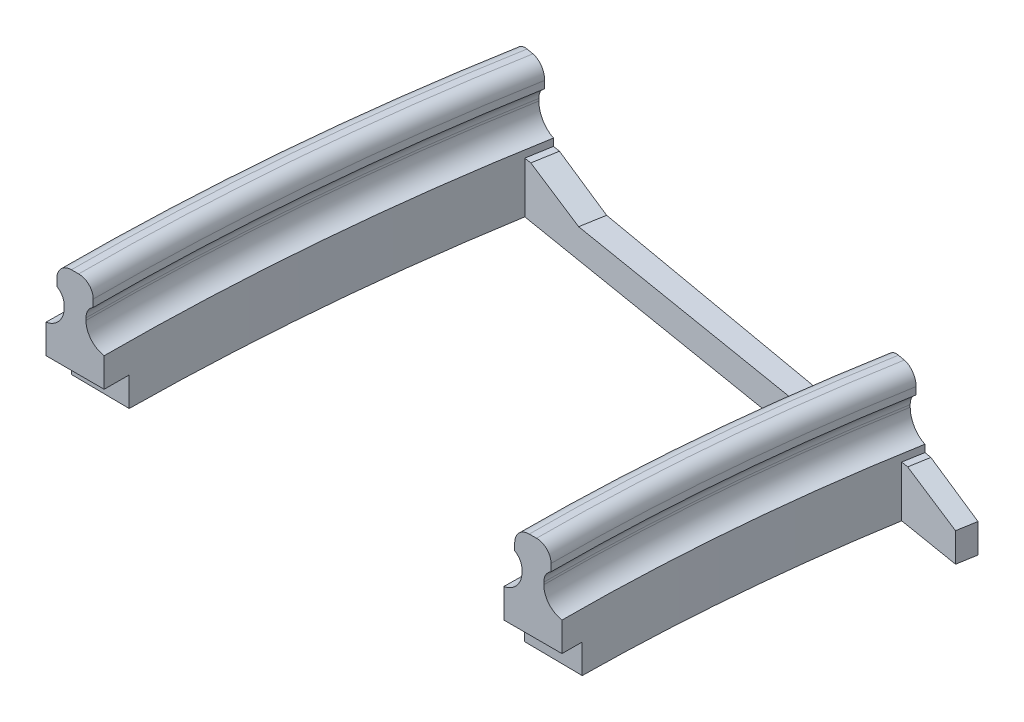
SolidWorks part; units mm, degrees
other "标注1"
sketch "草图3" plane through (-22.25, 4, -10) normal (-0.231, 0.6469, -0.7268) x (-0.9696, -0.2151, 0.1167)
ref_plane "前视基准面" through (0, 0, 0) normal (0, 0, 1) x (1, 0, 0)
ref_plane "上视基准面" through (0, 0, 0) normal (0, 1, 0) x (1, 0, 0)
ref_plane "右视基准面" through (0, 0, 0) normal (1, 0, 0) x (0, 0, -1)
other "Configuration Table"
sketch "草图4" plane through (0, 0, 0) normal (0, 0, 1) x (1, 0, 0)
  line L0 (0, 0) -> (31.5, 0) construction
  line L1 (0.75, -1.5) -> (1.25, -1.5)
  line L3 (0, 0) -> (1.25, 0)
  line L4 (1.25, -1.5) -> (1.25, 0)
  line L5 (0, 0) -> (-1.25, 0)
  line L10 (0.75, -1.5) -> (0.75, -4)
  line L11 (-0.75, -1.5) -> (-1.25, -1.5)
  line L12 (0.75, -4) -> (2, -4)
  line L14 (0, -8) -> (2, -8)
  line L15 (2, -4) -> (2, -8)
  line L16 (-1.25, 0) -> (-1.25, -1.5)
  line L20 (-0.75, -1.5) -> (-0.75, -4)
  line L21 (-0.75, -4) -> (-2, -4)
  line L23 (0, -8) -> (-2, -8)
  line L24 (-2, -4) -> (-2, -8)
  line L25 (31.5, 0) -> (32.75, 0)
  line L26 (30.25, 0) -> (31.5, 0)
  line L27 (30.25, 0) -> (30.25, -1.5)
  line L28 (30.25, -1.5) -> (30.75, -1.5)
  line L31 (30.75, -1.5) -> (30.75, -4)
  line L34 (29.5, -4) -> (30.75, -4)
  line L35 (29.5, -4) -> (29.5, -8)
  line L36 (29.5, -8) -> (31.5, -8)
  line L39 (32.25, -1.5) -> (32.75, -1.5)
  line L40 (32.75, 0) -> (32.75, -1.5)
  line L42 (32.25, -1.5) -> (32.25, -4)
  line L45 (32.25, -4) -> (33.5, -4)
  line L47 (31.5, -8) -> (33.5, -8)
  line L48 (33.5, -4) -> (33.5, -8)
  point P0 (0, 0)
  point P2 (15.75, 0)
  dimension "D1" = 1.25
  dimension "D4" = 2.5
sketch "草图6" plane through (0, 0, 0) normal (0, 0, 1) x (1, 0, 0)
  line L0 (165.75, 3.8535) -> (165.75, -12.2756)
  dimension "D1" = 150
revolve "旋转1" add sketch "草图4" angle 10 about L0
fillet "圆角1" radius 1.5 2 edges at (1.3779, -4, -14.3807) (-0.1164, -4, -14.5114)
fillet "圆角2" radius 1.5 2 edges at (31.2637, -4, -11.766) (32.758, -4, -11.6353)
fillet "圆角3" radius 1 4 edges at (33.2561, 0, -11.5917) (30.7656, 0, -11.8096) (31.2637, -1.5, -11.766) (32.758, -1.5, -11.6353)
fillet "圆角4" radius 1 4 edges at (1.876, 0, -14.3371) (-0.1164, -1.5, -14.5114) (1.3779, -1.5, -14.3807) (-0.6145, 0, -14.555)
sketch "草图7" plane through (0, 0, 0) normal (0, 0, 1) x (1, 0, 0)
  line L1 (-2, -8) -> (2, -8)
  line L2 (-2, -8) -> (-2, -6)
  line L3 (-2, -6) -> (2, -6)
  line L4 (2, -8) -> (2, -6)
  line L5 (33.5, -8) -> (33.5, -4) construction
  line L6 (29.5, -8) -> (33.5, -8)
  line L7 (29.5, -8) -> (29.5, -6)
  line L8 (29.5, -6) -> (33.5, -6)
  line L9 (33.5, -8) -> (33.5, -6)
  line L10 (2, -8) -> (2, -4) construction
  dimension "D1" = 2
sketch "草图9" plane through (0, 0, 0) normal (0, 1, 0) x (1, 0, 0)
  line L0 (29.5, 0) -> (2, 0)
  line L1 (-2, 0) -> (2, 0) construction
  line L2 (4.4877, 28.4349) -> (31.5699, 23.6596)
  line L3 (18.0288, 26.0472) -> (15.75, 0)
  arc A0 (4.4877, 28.4349) -> (2, 0) centre (165.75, 0) ccw construction
  arc A1 (31.5699, 23.6596) -> (29.5, 0) centre (165.75, 0) ccw construction
  point P20 (165.75, 0)
  dimension "D1" = 10
  dimension "D2" = 26.1467
revolve "切除-旋转1" cut sketch "草图7" angle 0.6 about L0
sketch "草图10" plane through (0, -6, 0) normal (0, -1, 0) x (1, 0, 0)
  line L0 (-1.9977, -0.8783) -> (2.0022, -0.8574) construction
  line L2 (2.0022, -0.8574) -> (29.5019, -0.7134) construction
  line L3 (29.5019, -0.7134) -> (33.5018, -0.6925) construction
  circle A1 centre (0.0023, -0.8679) radius 0.4
  circle A2 centre (31.5018, -0.7029) radius 0.4
  arc A3 (-2, 0) -> (-1.9908, -1.7566) centre (165.75, 0) ccw construction
  arc A4 (2, 0) -> (2.009, -1.7148) centre (165.75, 0) ccw construction
  arc A5 (29.5, 0) -> (29.5075, -1.4268) centre (165.75, 0) ccw construction
  arc A6 (33.5, 0) -> (33.5073, -1.3849) centre (165.75, 0) ccw construction
  point P10 (0, 0)
  point P24 (0, 0)
  dimension "D1" = 0.8
extrude "切除-拉伸1" cut sketch "草图10" against normal blind 2
sketch "草图11" plane through (4.998, 0, -28.3449) normal (0.1736, 0, -0.9848) x (-0.9848, 0, -0.1736)
  line L0 (-26.9819, -4.5) -> (-26.4819, -4.5)
  line L1 (-26.9819, -4) -> (-26.9819, -8) construction
  line L2 (-26.4819, -4.5) -> (-22.4819, -6)
  line L3 (-22.4819, -6) -> (-3.9819, -6)
  line L4 (-3.9819, -6) -> (0.0181, -4.5)
  line L5 (0.0181, -4.5) -> (0.5181, -4.5)
  line L6 (0.5181, -8) -> (0.5181, -4) construction
  line L7 (0.5181, -4.5) -> (4.5181, -4.5)
  line L8 (4.5181, -4) -> (4.5181, -8) construction
  line L9 (4.5181, -4.5) -> (5.0181, -4.5)
  line L10 (5.0181, -4.5) -> (9.0181, -6)
  line L11 (9.0181, -6) -> (9.0181, -8)
  line L13 (-35.4819, -8) -> (-35.4819, -6)
  line L14 (-35.4819, -6) -> (-31.4819, -4.5)
  line L15 (-31.4819, -4.5) -> (-30.9819, -4.5)
  line L16 (-30.9819, -8) -> (-30.9819, -4) construction
  line L17 (-30.9819, -4.5) -> (-26.9819, -4.5)
  line L19 (-35.4819, -8) -> (-30.9819, -8)
  line L20 (-30.9819, -8) -> (-26.9819, -8)
  line L21 (-26.9819, -8) -> (0.5181, -8)
  line L22 (0.5181, -8) -> (4.5181, -8)
  line L23 (4.5181, -8) -> (9.0181, -8)
  dimension "D1" = 0.5
  dimension "D2" = 4.5
  dimension "D3" = 3.5
  dimension "D4" = 2
revolve "旋转2" add sketch "草图11" angle 0.6 about L0 reverse direction yes
